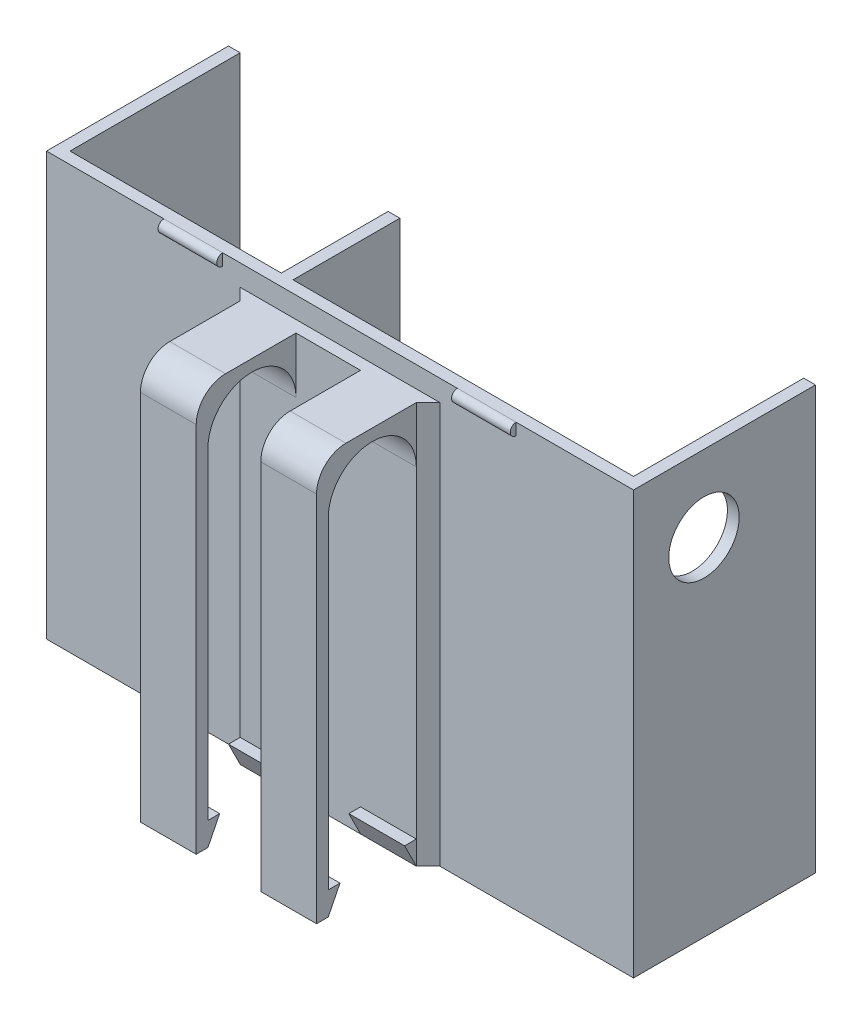
SolidWorks part; units mm, degrees
note: The reader was unsure of these and kept them because the rebuilt part matched: shared geometry of "Sketch3<3>", "Sketch5<3>", "Sketch5<4>".
ref_plane "Front Plane" through (0, 0, 0) normal (0, 0, 1) x (1, 0, 0)
ref_plane "Top Plane" through (0, 0, 0) normal (0, 1, 0) x (1, 0, 0)
ref_plane "Right Plane" through (0, 0, 0) normal (1, 0, 0) x (0, 0, -1)
sketch "Sketch1" plane through (0, 0, 0) normal (1, 0, 0) x (0, 0, -1)
  line L0 (0, 0) -> (0, 58.9)
  line L1 (0, 58.9) -> (15, 58.9)
  line L2 (15, 58.9) -> (15, 0)
  line L3 (0, 0) -> (-2, 0)
  line L4 (-2, 0) -> (-2, 58.9)
  line L5 (15, 0) -> (17, 0)
  line L6 (17, 0) -> (17, 58.9)
  line L7 (15, 0) -> (13, 4)
  line L8 (13, 4) -> (15, 4)
  line L9 (7.5, 68.4) -> (7.5, -6.29) construction
  line L10 (0, 0) -> (2, 4)
  line L11 (2, 4) -> (0, 4)
  line L12 (17, 58.9) -> (17, 68.4)
  line L13 (17, 68.4) -> (-2, 68.4)
  line L14 (-2, 68.4) -> (-2, 58.9)
  arc A0 (0, 58.9) -> (15, 58.9) centre (7.5, 58.9) cw
  arc A1 (-2, 58.9) -> (17, 58.9) centre (7.5, 58.9) cw
  point P11 (7.5, 68.4)
  dimension "D3" = 2
  dimension "D5" = 2
  dimension "D4" = 4
  dimension "D1" = 68.4
  dimension "D6" = 9.5
  dimension "D2" = 15
extrude "Boss-Extrude1" add sketch "Sketch1" against normal blind 30 contours A1 L4 L3 L0 A0 L2 L5 L6 | L9 A1 L4 L3 L0 A0 | L10 L11 L0 | L8 L7 L2 | L13 A1 L12 | L14 A1 L13
fillet "Fillet1" radius 5 1 edges at (-15, 68.4, 2)
sketch "Sketch2" plane through (0, 0, 2) normal (0, 0, 1) x (1, 0, 0)
  line L0 (-15, 68.4) -> (-15, 0) construction
  line L2 (-30, 0) -> (0, 0) construction
  line L4 (-20.5, 68.4) -> (-20.5, 0)
  line L5 (-20.5, 68.4) -> (-9.5, 68.4)
  line L6 (-15, 68.4) -> (-15, 0)
  line L7 (-9.5, 0) -> (-20.5, 0)
  line L8 (-9.5, 68.4) -> (-9.5, 0)
  dimension "D1" = 5.5
extrude "Cut-Extrude1" cut sketch "Sketch2" against normal blind 17
sketch "Sketch3" plane through (0, 0, -17) normal (0, 0, -1) x (-1, 0, 0)
  line L0 (15, 74) -> (15, 0) construction
  line L1 (63, 72) -> (65, 72)
  line L2 (30, 0) -> (0, 0) construction
  line L3 (-35, 0) -> (65, 0)
  line L4 (65, 0) -> (65, 74)
  line L5 (65, 74) -> (-35, 74)
  line L6 (-35, 0) -> (-35, 74)
  line L7 (-33, 2) -> (63, 2)
  line L8 (-33, 2) -> (-33, 72)
  line L9 (-33, 72) -> (63, 72)
  line L10 (63, 2) -> (63, 72)
  line L11 (-33, 2) -> (63, 72) construction
  line L12 (-33, 72) -> (63, 2) construction
  line L13 (-33, 72) -> (-35, 72)
  point P2 (15, 37)
  point P3 (15, 37)
  line M10 (0, 68.4) -> (0, 0)
  line M11 (0, 0) -> (30, 0)
  line M12 (30, 0) -> (30, 68.4)
  line M14 (30, 68.4) -> (0, 68.4)
  dimension "D1" = 100
  dimension "D2" = 74
  dimension "D3" = 70
  dimension "D4" = 96
extrude "Boss-Extrude3" add sketch "Sketch3" along normal blind 2 contours L7 L10 L9 L8 M10 M14 M12 | L10 L7 L3 L4 L5 L6 L8 L9 M12 M10 | L7 M10 M12 M14 | L7 M10 M11 M12
extrude "Boss-Extrude4" add sketch "Sketch3<3>" along normal blind 31 contours L8 L13 L6 L3 L7 M10 | L10 L7 L3 L4 L1 M12 | L7 M10 M11 M12
sketch "Sketch3<3>" plane through (0, 0, -17) normal (0, 0, -1) x (-1, 0, 0) same geometry as "Sketch3"
sketch "Sketch4" plane through (0, 0, -19) normal (0, 0, -1) x (-1, 0, 0)
  line L5 (-33, 2) -> (63, 2) construction
  line L6 (25, 2) -> (27, 2)
  line L7 (25, 2) -> (25, 72)
  line L8 (25, 72) -> (27, 72)
  line L9 (27, 2) -> (27, 72)
  line L10 (-33, 72) -> (63, 72) construction
  line L11 (63, 72) -> (63, 2) construction
  dimension "D1" = 2
  dimension "D2" = 38
extrude "Boss-Extrude5" add sketch "Sketch4" along normal blind 18.2
ref_plane "Plane1" through (-15, 0, 0) normal (-1, 0, 0) x (0, 0, 1)
sketch "Sketch5" plane through (-15, 0, 0) normal (-1, 0, 0) x (0, 0, 1)
  line L0 (-17, 72) -> (-17, 70)
  line L1 (-17, 0) -> (-17, 72) construction
  line L2 (-47.8, 0) -> (-45.8, 0)
  line L4 (-48, 0) -> (-17, 0) construction
  line L5 (-48, 0) -> (-48, 72) construction
  arc A0 (-17, 72) -> (-17, 70) centre (-17, 71) cw
  arc A1 (-47.8, 0) -> (-45.8, 0) centre (-46.8, 0) ccw
  dimension "D1" = 1
  dimension "D2" = 2
  dimension "D3" = 1.2
extrude "Boss-Extrude6" add sketch "Sketch5" along normal blind 10 and the other way blind 10 contours L2 A1
extrude "Boss-Extrude7" add sketch "Sketch5<3>" along normal blind 10 from offset 20 contours A0 L0
sketch "Sketch5<3>" plane through (-15, 0, 0) normal (-1, 0, 0) x (0, 0, 1) same geometry as "Sketch5"
extrude "Boss-Extrude8" add sketch "Sketch5<4>" against normal blind 10 from offset 20 contours A0 L0 offset against normal yes
sketch "Sketch5<4>" plane through (-15, 0, 0) normal (-1, 0, 0) x (0, 0, 1) same geometry as "Sketch5"
chamfer "Chamfer1" distance 2 angle 45 2 edges at (-30, 34.2, -17) (0, 34.2, -17)
sketch "Sketch6" plane through (35, 0, 0) normal (1, 0, 0) x (0, 0, -1)
  line L1 (48, 72) -> (17, 72) construction
  line L3 (17, 0) -> (17, 72) construction
  circle A0 centre (29, 59) radius 6
  dimension "D1" = 12
  dimension "D2" = 13
  dimension "D3" = 12
extrude "Cut-Extrude2" cut sketch "Sketch6" against normal up to next
